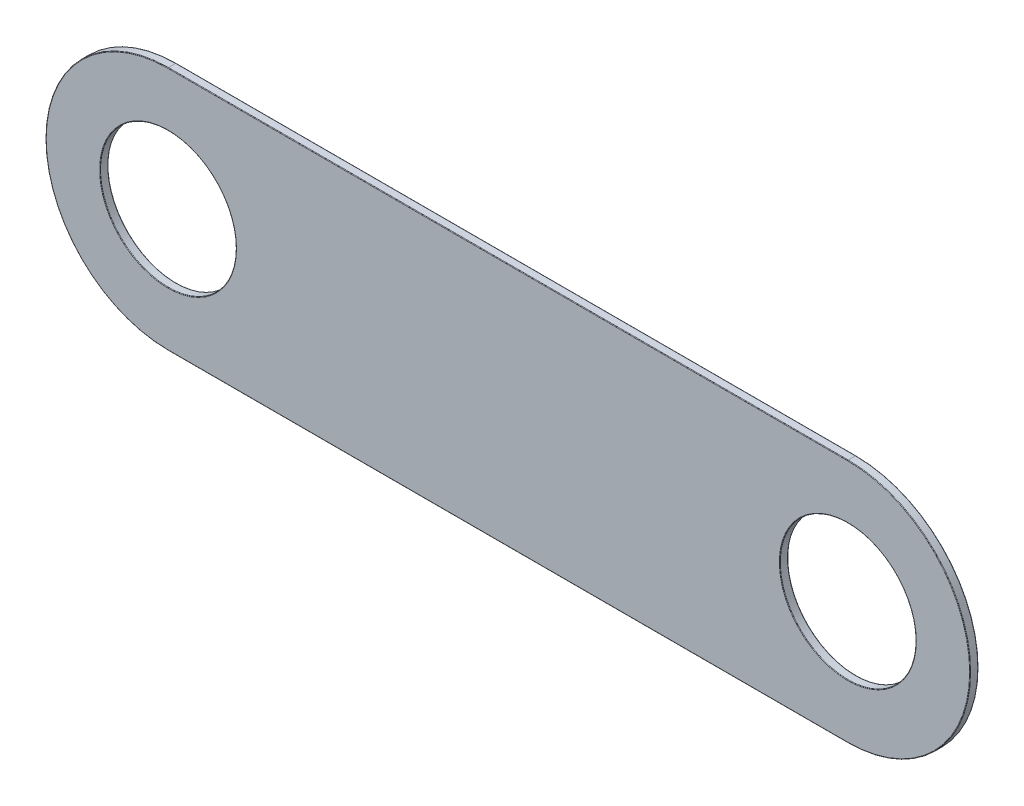
SolidWorks part; units mm, degrees
ref_plane "Front Plane" through (0, 0, 0) normal (0, 0, 1) x (1, 0, 0)
ref_plane "Top Plane" through (0, 0, 0) normal (0, 1, 0) x (1, 0, 0)
ref_plane "Right Plane" through (0, 0, 0) normal (1, 0, 0) x (0, 0, -1)
sketch "Sketch1" plane through (0, 0, 0) normal (0, 0, 1) x (1, 0, 0)
  line L0 (0, 0) -> (-12.5, 0) construction
  line L1 (0, -2.25) -> (-12.5, -2.25)
  line L2 (0, 2.25) -> (-12.5, 2.25)
  arc A0 (0, -2.25) -> (0, 2.25) centre (0, 0) ccw
  arc A1 (-12.5, 2.25) -> (-12.5, -2.25) centre (-12.5, 0) ccw
  circle A2 centre (-12.5, 0) radius 1.25
  circle A3 centre (0, 0) radius 1.25
  point P3 (-6.25, 0)
  dimension "D3" = 2.5
  dimension "D1" = 12.5
  dimension "D2" = 4.5
base flange "Base-Flange1" sketch "Sketch1" thickness 0.15 reverse thickness direction no parameters "D1"=1
fillet "Fillet1" radius 0.01 12 edges at (-6.25, 2.25, -0.15) (-14.75, 0, -0.15) (-6.25, -2.25, -0.15) (2.25, 0, -0.15) (-11.25, 0, -0.15) (1.25, 0, -0.15) (-6.25, -2.25, 0) (-14.75, 0, 0) (-6.25, 2.25, 0) (2.25, 0, 0) (-11.25, 0, 0) (1.25, 0, 0)
sketch "Bend-Lines1" plane through (0, 0, 0) normal (0, 1, 0) x (1, 0, 0)
sketch "Bounding-Box1" plane through (0, 0, 0) normal (0, 1, 0) x (1, 0, 0)
sheet metal parameters "Sheet-Metal1" thickness 0.15 parameters "D1"=1
flat pattern "Flat-Pattern1" [suppressed]
sketch "Bend-Lines2" plane through (0, 0, 0) normal (0, 1, 0) x (1, 0, 0)
sketch "Bounding-Box2" [suppressed] plane through (0, 0, 0) normal (0, 1, 0) x (1, 0, 0)
